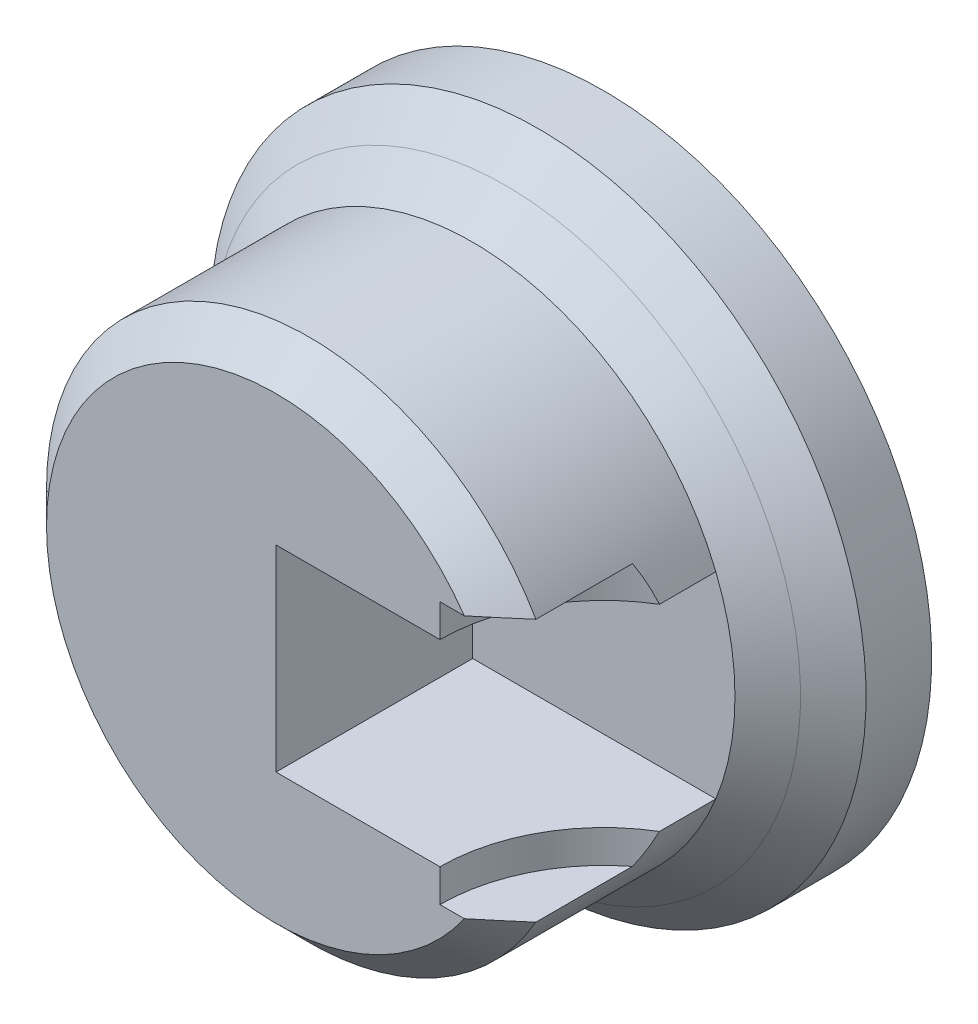
SolidWorks part; units mm, degrees
ref_plane "Front Plane" through (0, 0, 0) normal (0, 0, 1) x (1, 0, 0)
ref_plane "Top Plane" through (0, 0, 0) normal (0, 1, 0) x (1, 0, 0)
ref_plane "Right Plane" through (0, 0, 0) normal (1, 0, 0) x (0, 0, -1)
sketch "Sketch1" plane through (0, 0, 0) normal (0, 0, 1) x (1, 0, 0)
  circle A0 centre (0, 0) radius 4
  dimension "D1" = 8
extrude "Boss-Extrude1" add sketch "Sketch1" along normal blind 2.5 and the other way blind 2.5
sketch "Sketch2" plane through (0, 0, 2.5) normal (0, 0, 1) x (1, 0, 0)
  line L1 (8, -1.5) -> (8, 1.5)
  line L2 (8, -1.5) -> (0, -1.5)
  line L3 (0, -1.5) -> (0, 1.5)
  line L4 (8, 1.5) -> (0, 1.5)
  line L5 (8, -1.5) -> (0, 1.5) construction
  line L6 (0, -1.5) -> (8, 1.5) construction
  circle A0 centre (0, 0) radius 4 construction
  point P0 (4, 0)
  point P7 (0.4366, -3.9761)
  point P9 (0, 0)
  point P10 (0, 0)
  point P11 (7.9843, -1.4184)
  dimension "D1" = 3
extrude "Cut-Extrude1" cut sketch "Sketch2" against normal blind 3
sketch "Sketch3" plane through (0, 0, 0) normal (0, 1, 0) x (1, 0, 0)
  line L0 (0, 0) -> (0, -2.5) construction
  line L1 (0, -2.5) -> (5, -2.5) construction
  circle A0 centre (5, -2.5) radius 2.5
  dimension "D2" = 5
  dimension "D1" = 5
extrude "Cut-Extrude2" cut sketch "Sketch3" against normal blind 2 and the other way blind 2
chamfer "Chamfer1" distance 0.5 angle 45 1 edges at (-4, 0, 2.5)
sketch "Sketch4" plane through (0, 0, -2.5) normal (0, 0, -1) x (-1, 0, 0)
  circle A0 centre (0, 0) radius 5
  circle A1 centre (0, 0) radius 4 construction
  dimension "D1" = 1
extrude "Boss-Extrude2" add sketch "Sketch4" against normal blind 1.5
chamfer "Chamfer2" distance 0.5 angle 45 1 edges at (-4, 0, -1)
chamfer "Chamfer3" distance 0.5 angle 45 1 edges at (-5, 0, -1)
